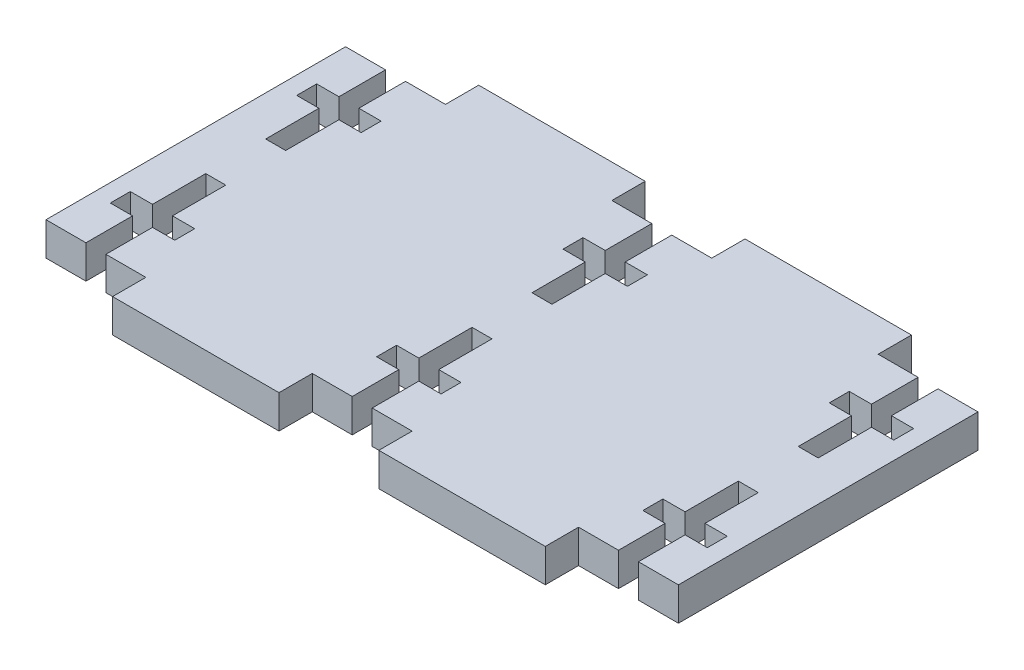
SolidWorks part; units mm, degrees
material "PVC rigido"
ref_plane "Piano frontale" through (0, 0, 0) normal (0, 0, 1) x (1, 0, 0)
ref_plane "Piano superiore" through (0, 0, 0) normal (0, 1, 0) x (1, 0, 0)
ref_plane "Piano destro" through (0, 0, 0) normal (1, 0, 0) x (0, 0, -1)
sketch "Schizzo1" plane through (0, 0, 0) normal (0, 1, 0) x (1, 0, 0)
  line L1 (-54.5649, -28.2811) -> (40.4351, -28.2811)
  line L2 (-54.5649, -28.2811) -> (-54.5649, 26.7189)
  line L3 (-54.5649, 26.7189) -> (40.4351, 26.7189)
  line L4 (40.4351, -28.2811) -> (40.4351, 26.7189)
  dimension "D1" = 95
  dimension "D2" = 55
sketch "Schizzo2" plane through (0, 0, 0) normal (0, 1, 0) x (1, 0, 0)
  line L0 (-54.5649, -0.7811) -> (40.4351, -0.7811) construction
  line L1 (-54.5649, -28.2811) -> (-39.5649, -28.2811)
  line L2 (-54.5649, -28.2811) -> (-54.5649, -23.2811)
  line L3 (-54.5649, -23.2811) -> (-39.5649, -23.2811)
  line L4 (-39.5649, -28.2811) -> (-39.5649, -23.2811)
  line L5 (-54.5649, -28.2811) -> (-54.5649, 26.7189) construction
  line L6 (40.4351, -28.2811) -> (40.4351, 26.7189) construction
  line L7 (-7.0649, -28.2811) -> (-7.0649, 26.7189) construction
  line L8 (-54.5649, -28.2811) -> (40.4351, -28.2811) construction
  line L9 (-54.5649, 26.7189) -> (40.4351, 26.7189) construction
  line L10 (-54.5649, 26.7189) -> (-54.5649, 21.7189)
  line L11 (-54.5649, 26.7189) -> (-39.5649, 26.7189)
  line L12 (-39.5649, 26.7189) -> (-39.5649, 21.7189)
  line L13 (-54.5649, 21.7189) -> (-39.5649, 21.7189)
  line L14 (40.4351, -28.2811) -> (40.4351, -23.2811)
  line L15 (40.4351, -28.2811) -> (25.4351, -28.2811)
  line L16 (25.4351, -28.2811) -> (25.4351, -23.2811)
  line L17 (40.4351, -23.2811) -> (25.4351, -23.2811)
  line L18 (40.4351, 26.7189) -> (40.4351, 21.7189)
  line L19 (40.4351, 26.7189) -> (25.4351, 26.7189)
  line L20 (25.4351, 26.7189) -> (25.4351, 21.7189)
  line L21 (40.4351, 21.7189) -> (25.4351, 21.7189)
  line L22 (-14.5649, -28.2811) -> (0.4351, -28.2811)
  line L23 (-14.5649, -28.2811) -> (-14.5649, -23.2811)
  line L24 (-14.5649, -23.2811) -> (0.4351, -23.2811)
  line L25 (0.4351, -28.2811) -> (0.4351, -23.2811)
  line L26 (-14.5649, 26.7189) -> (-14.5649, 21.7189)
  line L27 (-14.5649, 21.7189) -> (0.4351, 21.7189)
  line L28 (0.4351, 26.7189) -> (0.4351, 21.7189)
  line L29 (-14.5649, 26.7189) -> (0.4351, 26.7189)
  point P33 (-7.0649, -23.2811)
  dimension "D1" = 15
  dimension "D2" = 5
  dimension "D3" = 15
  dimension "D4" = 5
extrude "Estrusione-Estrusione2" add sketch "Schizzo1" against normal blind 5
extrude "Taglio-Estrusione1" cut sketch "Schizzo2" against normal through all
sketch "Schizzo3" plane through (0, 0, 0) normal (0, 1, 0) x (1, 0, 0)
  line L0 (-48.5649, -23.2811) -> (-45.5649, -23.2811)
  line L1 (-8.5649, -23.2811) -> (-5.5649, -23.2811)
  line L2 (-54.5649, -0.7811) -> (40.4351, -0.7811) construction
  line L3 (-54.5649, 21.7189) -> (-54.5649, -23.2811) construction
  line L4 (-48.5649, -23.2811) -> (-48.5649, -16.2811)
  line L5 (-48.5649, -16.2811) -> (-51.9049, -16.2811)
  line L6 (-51.9049, -16.2811) -> (-51.9049, -13.2811)
  line L7 (-51.9049, -13.2811) -> (-48.5649, -13.2811)
  line L8 (-48.5649, -13.2811) -> (-48.5649, -5.2811)
  line L9 (-48.5649, -5.2811) -> (-45.5649, -5.2811)
  line L10 (-45.5649, -5.2811) -> (-45.5649, -13.2811)
  line L11 (-45.5649, -13.2811) -> (-42.2249, -13.2811)
  line L12 (-42.2249, -13.2811) -> (-42.2249, -16.2811)
  line L13 (-42.2249, -16.2811) -> (-45.5649, -16.2811)
  line L14 (-45.5649, -16.2811) -> (-45.5649, -23.2811)
  line L15 (40.4351, -23.2811) -> (40.4351, 21.7189) construction
  line L16 (-47.0649, 21.7189) -> (-47.0649, -23.2811) construction
  line L17 (-54.5649, 21.7189) -> (-39.5649, 21.7189) construction
  line L18 (-39.5649, -23.2811) -> (-54.5649, -23.2811) construction
  line L19 (-7.0649, 21.7189) -> (-7.0649, -23.2811) construction
  line L20 (-14.5649, 21.7189) -> (0.4351, 21.7189) construction
  line L21 (0.4351, -23.2811) -> (-14.5649, -23.2811) construction
  line L22 (32.9351, 21.7189) -> (32.9351, -23.2811) construction
  line L23 (25.4351, 21.7189) -> (40.4351, 21.7189) construction
  line L24 (40.4351, -23.2811) -> (25.4351, -23.2811) construction
  line L25 (31.4351, -23.2811) -> (34.4351, -23.2811)
  line L26 (-8.5649, -23.2811) -> (-8.5649, -16.2811)
  line L27 (-8.5649, -16.2811) -> (-11.9049, -16.2811)
  line L28 (-11.9049, -16.2811) -> (-11.9049, -13.2811)
  line L29 (-11.9049, -13.2811) -> (-8.5649, -13.2811)
  line L30 (-8.5649, -13.2811) -> (-8.5649, -5.2811)
  line L31 (-8.5649, -5.2811) -> (-5.5649, -5.2811)
  line L32 (-5.5649, -5.2811) -> (-5.5649, -13.2811)
  line L33 (-5.5649, -13.2811) -> (-2.2249, -13.2811)
  line L34 (-2.2249, -13.2811) -> (-2.2249, -16.2811)
  line L35 (-2.2249, -16.2811) -> (-5.5649, -16.2811)
  line L36 (-5.5649, -16.2811) -> (-5.5649, -23.2811)
  line L37 (31.4351, 3.7189) -> (34.4351, 3.7189)
  line L38 (31.4351, -23.2811) -> (31.4351, -16.2811)
  line L39 (31.4351, -16.2811) -> (28.0951, -16.2811)
  line L40 (28.0951, -16.2811) -> (28.0951, -13.2811)
  line L41 (28.0951, -13.2811) -> (31.4351, -13.2811)
  line L42 (31.4351, -13.2811) -> (31.4351, -5.2811)
  line L43 (31.4351, -5.2811) -> (34.4351, -5.2811)
  line L44 (34.4351, -5.2811) -> (34.4351, -13.2811)
  line L45 (34.4351, -13.2811) -> (37.7751, -13.2811)
  line L46 (37.7751, -13.2811) -> (37.7751, -16.2811)
  line L47 (37.7751, -16.2811) -> (34.4351, -16.2811)
  line L48 (34.4351, -16.2811) -> (34.4351, -23.2811)
  line L49 (31.4351, 11.7189) -> (31.4351, 3.7189)
  line L50 (28.0951, 11.7189) -> (31.4351, 11.7189)
  line L51 (28.0951, 14.7189) -> (28.0951, 11.7189)
  line L52 (31.4351, 14.7189) -> (28.0951, 14.7189)
  line L53 (31.4351, 21.7189) -> (31.4351, 14.7189)
  line L54 (31.4351, 21.7189) -> (34.4351, 21.7189)
  line L55 (34.4351, 14.7189) -> (34.4351, 21.7189)
  line L56 (37.7751, 14.7189) -> (34.4351, 14.7189)
  line L57 (37.7751, 11.7189) -> (37.7751, 14.7189)
  line L58 (34.4351, 11.7189) -> (37.7751, 11.7189)
  line L59 (34.4351, 3.7189) -> (34.4351, 11.7189)
  line L60 (-8.5649, 3.7189) -> (-5.5649, 3.7189)
  line L61 (-8.5649, 11.7189) -> (-8.5649, 3.7189)
  line L62 (-11.9049, 11.7189) -> (-8.5649, 11.7189)
  line L63 (-11.9049, 14.7189) -> (-11.9049, 11.7189)
  line L64 (-8.5649, 14.7189) -> (-11.9049, 14.7189)
  line L65 (-8.5649, 21.7189) -> (-8.5649, 14.7189)
  line L66 (-8.5649, 21.7189) -> (-5.5649, 21.7189)
  line L67 (-5.5649, 14.7189) -> (-5.5649, 21.7189)
  line L68 (-2.2249, 14.7189) -> (-5.5649, 14.7189)
  line L69 (-2.2249, 11.7189) -> (-2.2249, 14.7189)
  line L70 (-5.5649, 11.7189) -> (-2.2249, 11.7189)
  line L71 (-5.5649, 3.7189) -> (-5.5649, 11.7189)
  line L72 (-48.5649, 3.7189) -> (-45.5649, 3.7189)
  line L73 (-48.5649, 11.7189) -> (-48.5649, 3.7189)
  line L74 (-51.9049, 11.7189) -> (-48.5649, 11.7189)
  line L75 (-51.9049, 14.7189) -> (-51.9049, 11.7189)
  line L76 (-48.5649, 14.7189) -> (-51.9049, 14.7189)
  line L77 (-48.5649, 21.7189) -> (-48.5649, 14.7189)
  line L78 (-48.5649, 21.7189) -> (-45.5649, 21.7189)
  line L79 (-45.5649, 14.7189) -> (-45.5649, 21.7189)
  line L80 (-42.2249, 14.7189) -> (-45.5649, 14.7189)
  line L81 (-42.2249, 11.7189) -> (-42.2249, 14.7189)
  line L82 (-45.5649, 11.7189) -> (-42.2249, 11.7189)
  line L83 (-45.5649, 3.7189) -> (-45.5649, 11.7189)
  line L84 (-39.5649, 21.7189) -> (-39.5649, 26.7189) construction
  line L85 (-14.5649, 26.7189) -> (-14.5649, 21.7189) construction
  line L86 (0.4351, 21.7189) -> (0.4351, 26.7189) construction
  line L87 (25.4351, 26.7189) -> (25.4351, 21.7189) construction
  point P36 (-47.0649, -23.2811)
  point P53 (-7.0649, -23.2811)
  point P66 (32.9351, -23.2811)
  point P99 (-39.5649, 24.2189)
  point P102 (-14.5649, 24.2189)
  point P107 (25.4351, 24.2189)
  point P110 (0.4351, 24.2189)
  dimension "D1" = 8
  dimension "D2" = 3
  dimension "D3" = 3
  dimension "D4" = 7
  dimension "D5" = 3.34
  dimension "D6" = 40
  dimension "D7" = 40
  dimension "D8" = 3
  dimension "D9" = 7
  dimension "D10" = 8
  dimension "D11" = 3
  dimension "D12" = 3.34
  dimension "D13" = 3
  dimension "D14" = 7
  dimension "D15" = 8
  dimension "D16" = 3
  dimension "D17" = 3.34
  dimension "D18" = 25
  dimension "D19" = 25
extrude "Taglio-Estrusione3" cut sketch "Schizzo3" against normal through all
